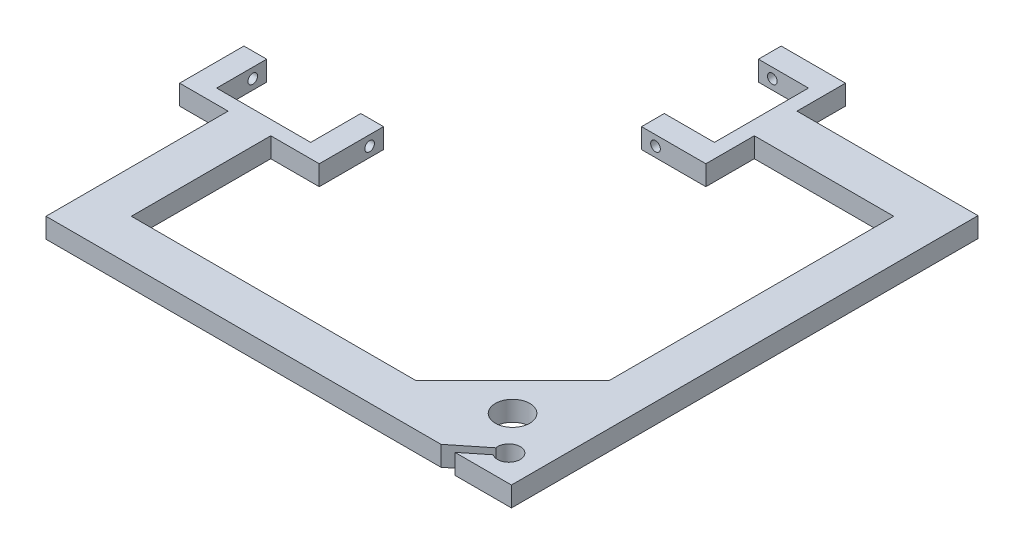
SolidWorks part; units mm, degrees
ref_plane "Front Plane" through (0, 0, 0) normal (0, 0, 1) x (1, 0, 0)
ref_plane "Top Plane" through (0, 0, 0) normal (0, 1, 0) x (1, 0, 0)
ref_plane "Right Plane" through (0, 0, 0) normal (1, 0, 0) x (0, 0, -1)
sketch "Sketch1" plane through (0, 0, 0) normal (0, 1, 0) x (1, 0, 0)
  line L0 (-86.41, -26.1652) -> (-86.41, -43.7652)
  line L1 (-86.41, -43.7652) -> (-53.34, -43.7652)
  line L2 (-53.34, -43.7652) -> (-53.34, -26.1652)
  line L3 (-53.34, -26.1652) -> (-45.34, -26.1652)
  line L4 (-45.34, -26.1652) -> (-45.34, -48.7652)
  line L5 (-45.34, -48.7652) -> (-62.375, -48.7652)
  line L6 (-86.41, -26.1652) -> (-94.41, -26.1652)
  line L7 (-94.41, -26.1652) -> (-94.41, -48.7652)
  line L8 (-94.41, -48.7652) -> (-77.375, -48.7652)
  line L9 (-77.375, -48.7652) -> (-77.375, -112.7652)
  line L10 (-62.375, -48.7652) -> (-62.375, -97.7652)
  line L11 (-77.375, -112.7652) -> (37.625, -112.7652)
  line L12 (-62.375, -97.7652) -> (37.625, -97.7652)
  line L14 (22.6, 36.2098) -> (22.6, 19.1748)
  line L15 (22.6, 19.1748) -> (0, 19.1748)
  line L16 (0, 19.1748) -> (0, 27.1748)
  line L17 (0, 27.1748) -> (17.6, 27.1748)
  line L18 (17.6, 27.1748) -> (17.6, 60.2448)
  line L19 (17.6, 60.2448) -> (0, 60.2448)
  line L20 (0, 60.2448) -> (0, 68.2448)
  line L21 (0, 68.2448) -> (22.6, 68.2448)
  line L22 (22.6, 68.2448) -> (22.6, 51.2098)
  line L28 (22.6, 36.2098) -> (71.6, 36.2098)
  line L29 (71.6, 36.2098) -> (71.6, -63.7902)
  line L30 (22.6, 51.2098) -> (86.215, 51.2098)
  line L31 (86.215, 51.2098) -> (86.215, -64.1752)
  line L32 (71.6, -63.7902) -> (37.625, -97.7652)
  line L34 (86.215, -112.7652) -> (86.215, -64.1752)
  line L35 (72.1405, -104.204) -> (61.4476, -112.7652)
  line L36 (66.35, -112.7652) -> (73.8211, -106.7835)
  line L37 (66.35, -112.7652) -> (86.215, -112.7652)
  line L38 (61.4476, -112.7652) -> (37.625, -112.7652)
  circle A2 centre (64.6, -90.7652) radius 6.05
  arc A3 (73.8211, -106.7835) -> (72.1405, -104.204) centre (76.045, -103.4975) ccw
  dimension "D11" = 7
  dimension "D12" = 7
  dimension "D13" = 12.1
  dimension "D1" = 8
  dimension "D2" = 17.6
  dimension "D3" = 5
  dimension "D4" = 33.07
  dimension "D5" = 100
  dimension "D6" = 15
  dimension "D7" = 49
  dimension "D8" = 15
  dimension "D9" = 70.94
  dimension "D10" = 70.94
  dimension "D14" = 4.9023
extrude "Boss-Extrude1" add sketch "Sketch1" along normal blind 7
sketch "Sketch2" plane through (0, 0, -19.1748) normal (0, 0, 1) x (1, 0, 0)
  line L0 (0, 7) -> (0, 0) construction
  line L1 (0, 7) -> (22.6, 7) construction
  line L3 (0, 0) -> (22.6, 0) construction
  circle A0 centre (4.9, 3.5) radius 1.7
  dimension "D1" = 3.4
  dimension "D2" = 4.9
  dimension "D3" = 3.5
  dimension "D4" = 3.5
extrude "Cut-Extrude1" cut sketch "Sketch2" against normal blind 60
sketch "Sketch3" plane through (-45.34, 0, 0) normal (1, 0, 0) x (0, 0, -1)
  line L0 (-26.1652, 7) -> (-26.1652, 0) construction
  line L1 (-48.7652, 7) -> (-26.1652, 7) construction
  line L2 (-48.7652, 0) -> (-26.1652, 0) construction
  circle A0 centre (-31.0652, 3.5) radius 1.7
  dimension "D1" = 3.4
  dimension "D3" = 3.5
  dimension "D4" = 3.5
  dimension "D2" = 4.9
extrude "Cut-Extrude2" cut sketch "Sketch3" against normal blind 60
